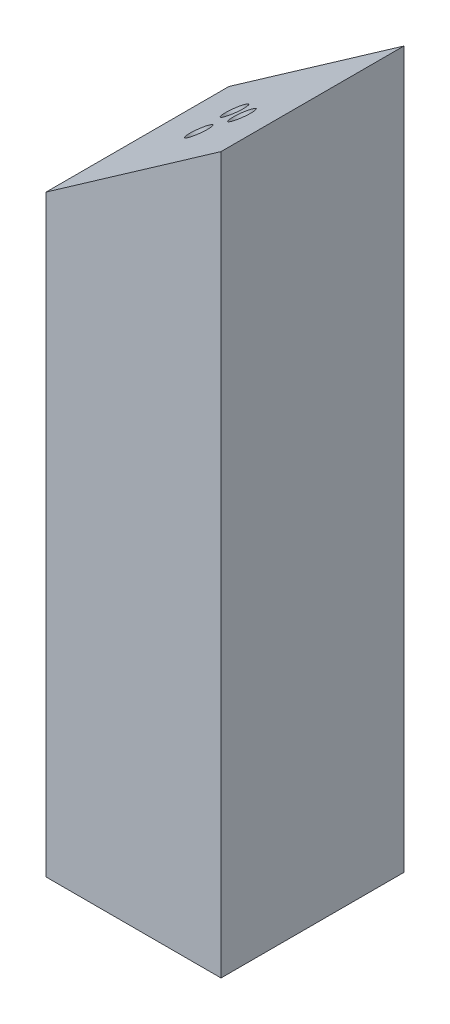
SolidWorks part; units mm, degrees
ref_plane "Front Plane" through (0, 0, 0) normal (0, 0, 1) x (1, 0, 0)
ref_plane "Top Plane" through (0, 0, 0) normal (0, 1, 0) x (1, 0, 0)
ref_plane "Right Plane" through (0, 0, 0) normal (1, 0, 0) x (0, 0, -1)
sketch "Sketch1" plane through (0, 0, 0) normal (0, 1, 0) x (1, 0, 0)
  line L0 (0, 63.205) -> (0, -68.0193) construction
  line L1 (-55, 57.5) -> (55, 57.5)
  line L2 (-55, 57.5) -> (-55, -57.5)
  line L3 (-55, -57.5) -> (55, -57.5)
  line L4 (55, 57.5) -> (55, -57.5)
  line L5 (-81.7056, 0) -> (95.5983, 0) construction
  dimension "D1" = 115
  dimension "D2" = 110
extrude "Boss-Extrude1" add sketch "Sketch1" along normal blind 350
sketch "Sketch2" plane through (0, 350, 0) normal (0, 1, 0) x (1, 0, 0)
  line L0 (55, -57.5) -> (55, 57.5) construction
  line L1 (-55, 57.5) -> (55, 57.5)
  line L2 (-55, 57.5) -> (-55, -57.5)
  line L3 (-55, -57.5) -> (55, -57.5)
  line L4 (55, 57.5) -> (55, -57.5)
  line L5 (-55, 57.5) -> (-55, -57.5) construction
  line L6 (55, 57.5) -> (-55, 57.5) construction
  line L7 (-55, -57.5) -> (55, -57.5) construction
extrude "Boss-Extrude2" add sketch "Sketch2" along normal blind 100
sketch "Sketch3" plane through (0, 0, 57.5) normal (0, 0, 1) x (1, 0, 0)
  line L0 (-55, 450) -> (55, 450)
  line L1 (55, 450) -> (-55, 372.9772)
  line L2 (-55, 372.9772) -> (-55, 450)
  line L3 (-55, 450) -> (-55, 0) construction
  line L4 (-55, 450) -> (55, 450) construction
  dimension "D1" = 35
extrude "Cut-Extrude1" cut sketch "Sketch3" against normal up to next
shell "Shell1" thickness 5 removed face at (0, 0, 0)
sketch "Sketch4" plane through (-193.3364, 276.113, 0) normal (-0.5736, 0.8192, 0) x (0.8192, 0.5736, 0)
  line L0 (236.0202, 101.3688) -> (236.0202, -153.5481) construction
  line L1 (347.0583, 0) -> (151.3464, 0) construction
  line L2 (168.8776, -57.5) -> (303.1628, -57.5) construction
  line L3 (303.1628, 57.5) -> (168.8776, 57.5) construction
  line L4 (168.8776, 57.5) -> (168.8776, -57.5) construction
  line L5 (303.1628, -57.5) -> (303.1628, 57.5) construction
  line L6 (236.0202, 0) -> (229.5202, 11.2583) construction
  circle A0 centre (236.0202, 0) radius 13 construction
  circle A1 centre (249.0202, 0) radius 7
  circle A2 centre (229.5202, -11.2583) radius 7
  circle A3 centre (229.5202, 11.2583) radius 7
  dimension "D1" = 26
  dimension "D2" = 14
  dimension "D3" = 14
  dimension "D4" = 14
  dimension "D5" = 120
extrude "Cut-Extrude2" cut sketch "Sketch4" against normal up to next
sketch "Sketch5" plane through (-55, 0, 0) normal (-1, 0, 0) x (0, 0, 1)
  line L0 (0, 0) -> (0, 504.2263) construction
  line L1 (-35, 362.9772) -> (35, 362.9772)
  line L2 (-35, 362.9772) -> (-35, 346.9772)
  line L3 (-35, 346.9772) -> (35, 346.9772)
  line L4 (35, 362.9772) -> (35, 346.9772)
  line L5 (-57.5, 372.9772) -> (57.5, 372.9772) construction
  dimension "D1" = 16
  dimension "D2" = 70
  dimension "D3" = 10
extrude "Cut-Extrude3" cut sketch "Sketch5" against normal up to next
fillet "Fillet1" radius 8 4 edges at (-52.5, 346.9772, 35) (-52.5, 362.9772, 35) (-52.5, 346.9772, -35) (-52.5, 362.9772, -35)
ref_plane "Plane1" through (0, 450, 0) normal (0, -1, 0) x (-1, 0, 0)
ref_plane "Plane2" through (0, 400, 0) normal (0, -1, 0) x (-1, 0, 0)
ref_plane "Plane3" through (0, 340, 0) normal (0, -1, 0) x (-1, 0, 0)
